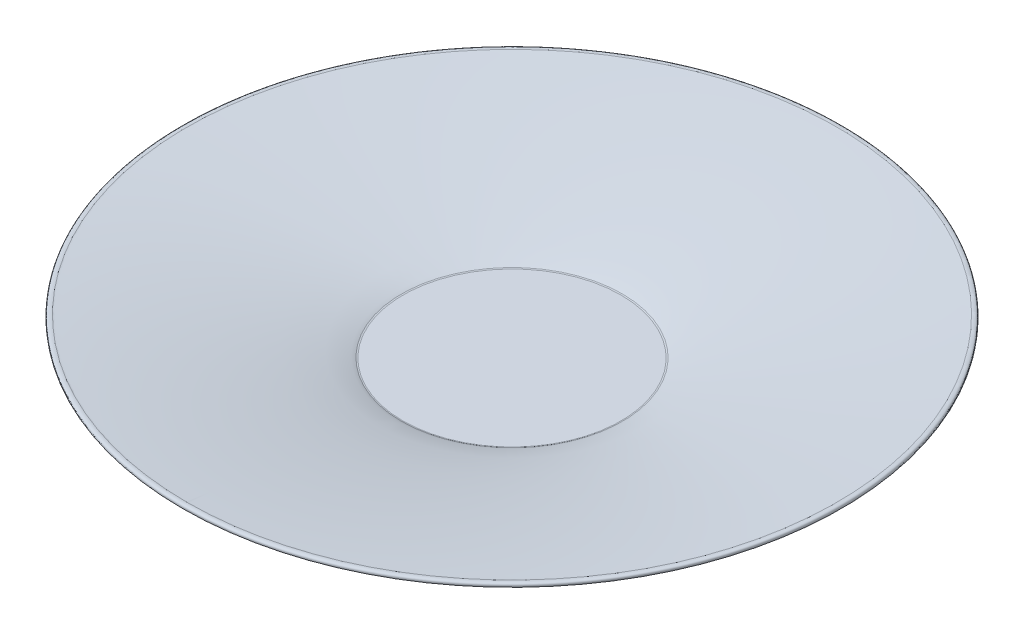
SolidWorks part; units mm, degrees
ref_plane "Front Plane" through (0, 0, 0) normal (0, 0, 1) x (1, 0, 0)
ref_plane "Top Plane" through (0, 0, 0) normal (0, 1, 0) x (1, 0, 0)
ref_plane "Right Plane" through (0, 0, 0) normal (1, 0, 0) x (0, 0, -1)
sketch "Sketch1" plane through (0, 0, 0) normal (0, 0, 1) x (1, 0, 0)
  line L2 (0, 0) -> (25, 0)
  line L3 (25, 0) -> (28, 1.561) construction
  line L4 (28, 1.561) -> (50, 6.3585) construction
  line L5 (50, 6.3585) -> (74, 8.4694) construction
  line L6 (74, 8.4694) -> (74, 8.5334) construction
  line L7 (0, 0) -> (0, -2.3763)
  line L8 (0, -2.3763) -> (25.8, -2.3763)
  line L9 (25.8, -2.3763) -> (25, -1.1882) construction
  line L10 (25, -1.1882) -> (28.3767, 0.5826) construction
  line L11 (28.3767, 0.5826) -> (50.4, 4.5663) construction
  line L12 (50.4, 4.5663) -> (75, 7.7979) construction
  spline S0 degree 4 poles (25, 0) (28, 1.561) (50, 6.3585) (74, 8.4694) (74, 8.5334) knots 0 0 0 0 0 1 1 1 1 1
  spline S1 degree 4 poles (25.8, -2.3763) (25, -1.1882) (28.3767, 0.5826) (50.4, 4.5663) (75, 7.7979) knots 0 0 0 0 0 1 1 1 1 1
  spline S2 degree 2 poles (74, 8.5334) (75.2335, 8.7362) (75, 7.7979) knots 0 0 0 1 1 1
  dimension "D1" = 25
  dimension "D2" = 25.8
  dimension "D3" = 28
  dimension "D4" = 28.3767
  dimension "D5" = 50
  dimension "D6" = 50.4
  dimension "D7" = 74
  dimension "D8" = 74
  dimension "D9" = 75
  dimension "D10" = 75
  dimension "D11" = 0.5826
  dimension "D12" = 1.561
  dimension "D13" = 4.5663
  dimension "D14" = 6.3585
  dimension "D15" = 7.7979
  dimension "D16" = 8.2796
  dimension "D17" = 8.4694
  dimension "D18" = 8.5334
  dimension "D19" = 1.1882
  dimension "D20" = 2.3763
revolve "Revolve1" add sketch "Sketch1" angle 360 about L7
sketch "Sketch2" plane through (0, -2.3763, 0) normal (0, -1, 0) x (1, 0, 0)
  circle A0 centre (0, 0) radius 30
  dimension "D1" = 60
extrude "Boss-Extrude1" add sketch "Sketch2" along normal blind 2
fillet "Fillet1" radius 3 1 edges at (0, -2.3763, -30)
fillet "Fillet3" radius 0.75 1 edges at (0, 0, 25)
fillet "Fillet4" radius 0.65 1 edges at (0, -2.3763, 25.8)
sketch "Sketch3" plane through (0, -4.3763, 0) normal (0, -1, 0) x (1, 0, 0)
  circle A0 centre (0, 0) radius 27
  dimension "D1" = 54
extrude "Cut-Extrude1" cut sketch "Sketch3" against normal blind 1
fillet "Fillet6" radius 0.65 1 edges at (0, -3.3763, -27)
